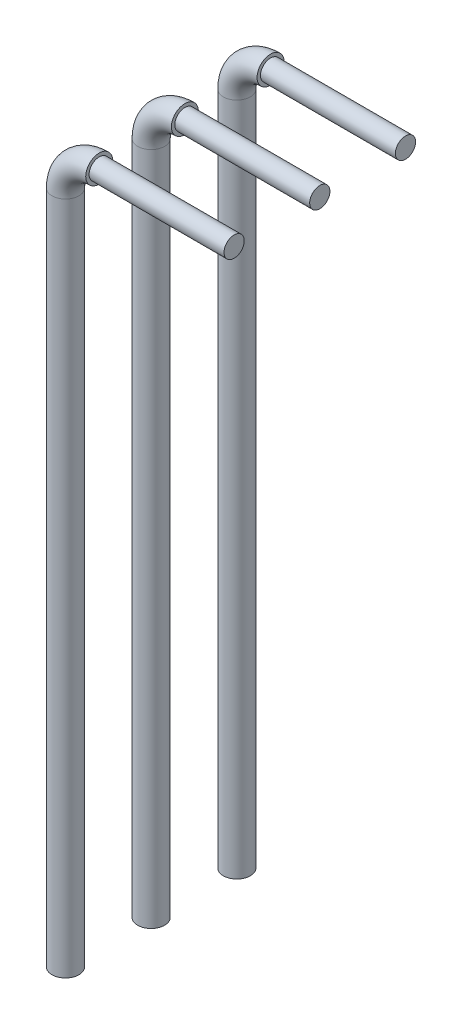
SolidWorks part; units mm, degrees
ref_plane "Plan de face" through (0, 0, 0) normal (0, 0, 1) x (1, 0, 0)
ref_plane "Plan de dessus" through (0, 0, 0) normal (0, 1, 0) x (1, 0, 0)
ref_plane "Plan de droite" through (0, 0, 0) normal (1, 0, 0) x (0, 0, -1)
sketch "Esquisse1" plane through (0, 0, 0) normal (0, 0, 1) x (1, 0, 0)
  line L0 (0, 0) -> (0, 20)
  arc A0 (0, 20) -> (1.0007, 21) centre (1, 20) cw
  dimension "D1" = 1
  dimension "D2" = 20
sketch "Esquisse2" plane through (0, 0, 0) normal (0, 1, 0) x (1, 0, 0)
  circle A0 centre (0, 0) radius 0.4
  dimension "D1" = 0.8
sweep "Balayage1" add profiles "Esquisse2" path "Esquisse1"
sketch "Esquisse3" plane through (0.9859, -0.0007, 0) normal (1, -0.0007, 0) x (0, 0, -1)
  circle A0 centre (0, 21.0007) radius 0.3
extrude "Boss.-Extru.1" add sketch "Esquisse3" along normal blind 4
ref_axis "Axe2" through (0, 0, 0.66) along (0, 0, -1)
pattern_linear "Répétition linéaire2" count 3 spacing 2.54 along (0, 0, -1) of "Balayage1", "Boss.-Extru.1"
